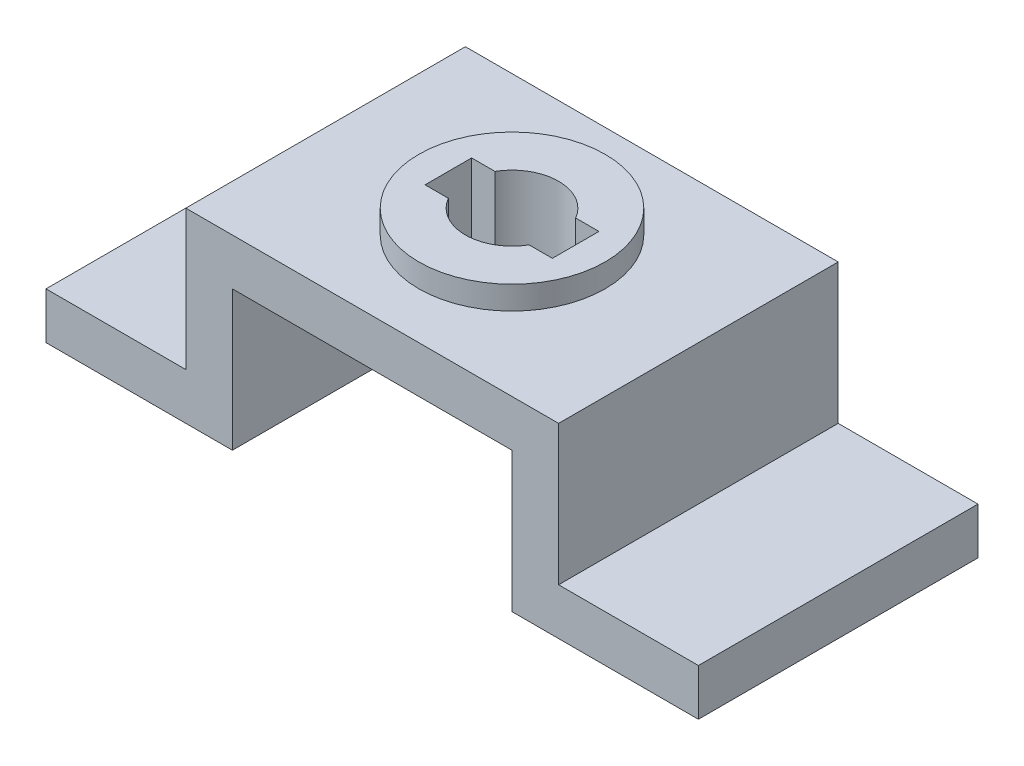
SolidWorks part; units mm, degrees
ref_plane "Ön Düzlem" through (0, 0, 0) normal (0, 0, 1) x (1, 0, 0)
ref_plane "Üst Düzlem" through (0, 0, 0) normal (0, 1, 0) x (1, 0, 0)
ref_plane "Sağ Düzlem" through (0, 0, 0) normal (1, 0, 0) x (0, 0, -1)
sketch "Çizim1" plane through (0, 0, 0) normal (0, 0, 1) x (1, 0, 0)
  line L1 (0, 0) -> (140, 0)
  line L2 (0, 0) -> (0, 40)
  line L3 (0, 40) -> (140, 40)
  line L4 (140, 0) -> (140, 40)
  dimension "D1" = 140
  dimension "D2" = 40
extrude "Yükseklik-Ekstrüzyon1" add sketch "Çizim1" along normal blind 60
sketch "Çizim2" plane through (0, 40, 0) normal (0, 1, 0) x (1, 0, 0)
  line L0 (140, -60) -> (0, -60) construction
  line L1 (0, 0) -> (30, 0)
  line L2 (0, 0) -> (0, -60)
  line L3 (0, -60) -> (30, -60)
  line L4 (30, 0) -> (30, -60)
  line L5 (70, 0) -> (70, -60) construction
  line L6 (140, 0) -> (0, 0) construction
  line L7 (110, 0) -> (110, -60)
  line L8 (140, -60) -> (110, -60)
  line L9 (140, 0) -> (140, -60)
  line L10 (140, 0) -> (110, 0)
  dimension "D1" = 30
extrude "Kes-Ekstrüzyon1" cut sketch "Çizim2" against normal blind 30
sketch "Çizim3" plane through (0, 0, 60) normal (0, 0, 1) x (1, 0, 0)
  line L0 (0, 0) -> (140, 0) construction
  line L1 (40, 0) -> (100, 0)
  line L2 (40, 0) -> (40, 30)
  line L3 (40, 30) -> (100, 30)
  line L4 (100, 0) -> (100, 30)
  line L5 (110, 40) -> (30, 40) construction
  line L6 (30, 10) -> (30, 40) construction
  line L7 (110, 10) -> (110, 40) construction
  dimension "D1" = 10
  dimension "D2" = 10
  dimension "D3" = 10
extrude "Kes-Ekstrüzyon2" cut sketch "Çizim3" against normal through all
sketch "Çizim4" plane through (0, 40, 0) normal (0, 1, 0) x (1, 0, 0)
  line L0 (110, -60) -> (30, -60) construction
  line L1 (70, 0) -> (70, -60) construction
  line L2 (110, 0) -> (30, 0) construction
  line L3 (30, -30) -> (110, -30) construction
  line L4 (30, -60) -> (30, 0) construction
  line L5 (110, 0) -> (110, -60) construction
  line L6 (56.3397, -25) -> (61.3397, -25)
  line L7 (56.3397, -35) -> (61.3397, -35)
  line L8 (56.3397, -25) -> (56.3397, -35)
  line L9 (83.6603, -35) -> (78.6603, -35)
  line L10 (83.6603, -25) -> (83.6603, -35)
  line L11 (83.6603, -25) -> (78.6603, -25)
  circle A0 centre (70, -30) radius 20
  arc A1 (61.3397, -35) -> (78.6603, -35) centre (70, -30) ccw
  arc A2 (78.6603, -25) -> (61.3397, -25) centre (70, -30) ccw
  point P14 (0, 0)
  point P19 (56.3397, -30)
  dimension "D1" = 40
  dimension "D2" = 20
  dimension "D3" = 5
  dimension "D4" = 5
extrude "Kes-Ekstrüzyon3" cut sketch "Çizim4" against normal through all contours A2 L6 L8 L7 A1 L9 L10 L11
extrude "Yükseklik-Ekstrüzyon2" add sketch "Çizim4<4>" along normal blind 5 contours A0 | L8 L7 A1 L9 L10 L11 A2 L6
sketch "Çizim4<4>" plane through (0, 40, 0) normal (0, 1, 0) x (1, 0, 0) same geometry as "Çizim4"
